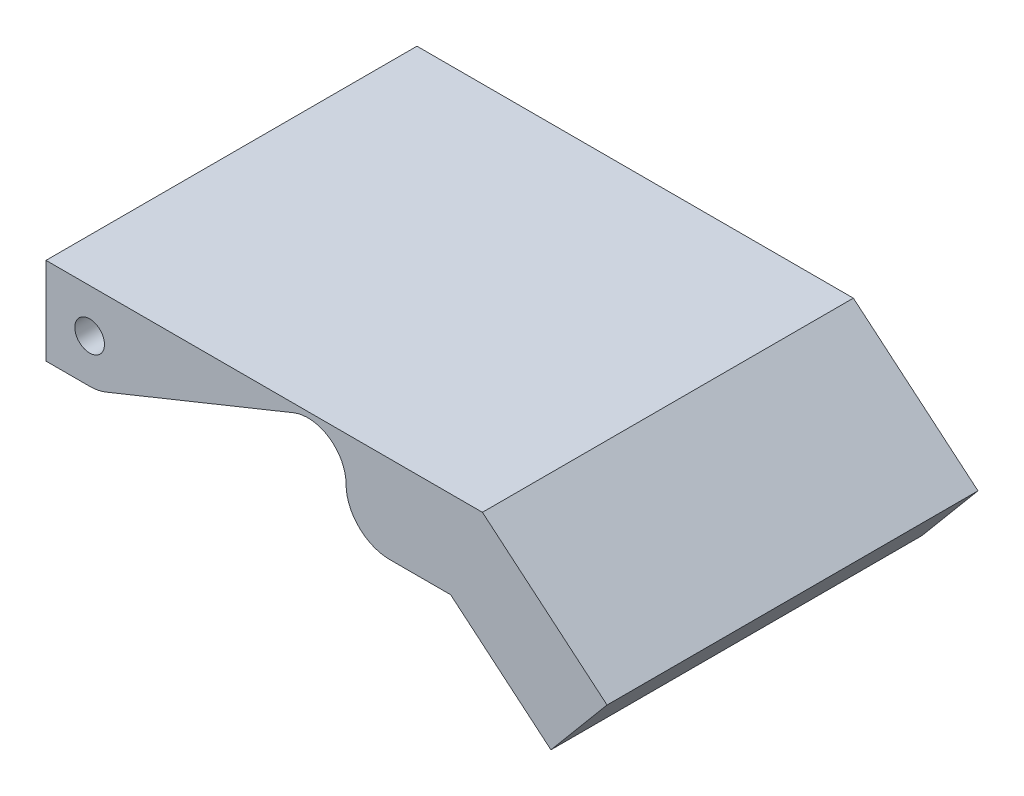
SolidWorks part; units mm, degrees
ref_plane "Front Plane" through (0, 0, 0) normal (0, 0, 1) x (1, 0, 0)
ref_plane "Top Plane" through (0, 0, 0) normal (0, 1, 0) x (1, 0, 0)
ref_plane "Right Plane" through (0, 0, 0) normal (1, 0, 0) x (0, 0, -1)
sketch "Sketch1" plane through (0, 0, 0) normal (0, 0, 1) x (1, 0, 0)
  line L0 (0, 0) -> (63.5, 0)
  line L1 (63.5, 0) -> (81.6341, -15.2163)
  line L2 (81.6341, -15.2163) -> (73.4707, -24.9451)
  line L3 (73.4707, -24.9451) -> (58.8776, -12.7)
  line L4 (58.8776, -12.7) -> (0, -12.7)
  line L5 (0, -12.7) -> (0, 0)
  point P6 (0, 0)
  dimension "D1" = 12.7
  dimension "D2" = 12.7
  dimension "D3" = 63.5
  dimension "D4" = 19.05
  dimension "D5" = 220
extrude "Boss-Extrude1" add sketch "Sketch1" along normal mid plane 53.975
sketch "Sketch2" plane through (0, 0, 26.9875) normal (0, 0, 1) x (1, 0, 0)
  line L0 (0, 0) -> (0, -12.7) construction
  line L1 (63.5, 0) -> (0, 0) construction
  circle A0 centre (6.35, -6.35) radius 2.159
  circle A1 centre (38.1, -6.35) radius 1.905
  point P8 (0, 0)
  dimension "D4" = 4.318
  dimension "D5" = 3.81
  dimension "D1" = 31.75
  dimension "D2" = 6.35
  dimension "D3" = 6.35
extrude "Cut-Extrude1" cut sketch "Sketch2" against normal through all
sketch "Sketch3" plane through (0, 0, 26.9875) normal (0, 0, 1) x (1, 0, 0)
  line L0 (8.7313, -12.2366) -> (36.0164, -1.1992)
  line L1 (6.35, -12.7) -> (50.0063, -12.7)
  line L2 (0, -12.7) -> (58.8776, -12.7) construction
  arc A0 (43.6562, -6.35) -> (36.0164, -1.1992) centre (38.1, -6.35) ccw
  arc A1 (6.35, -12.7) -> (8.7313, -12.2366) centre (6.35, -6.35) ccw
  arc A2 (43.6562, -6.35) -> (50.0063, -12.7) centre (50.0063, -6.35) ccw
  point P1 (10.2153, -13.7504)
  point P4 (50.7458, -12.7)
  point P10 (0, 0)
  point P15 (47.8749, -12.7)
  dimension "D1" = 11.1125
extrude "Cut-Extrude2" cut sketch "Sketch3" against normal blind 12.7
mirror "Mirror1" about plane through (0, 0, 0) normal (0, 0, 1) of "Cut-Extrude2"
